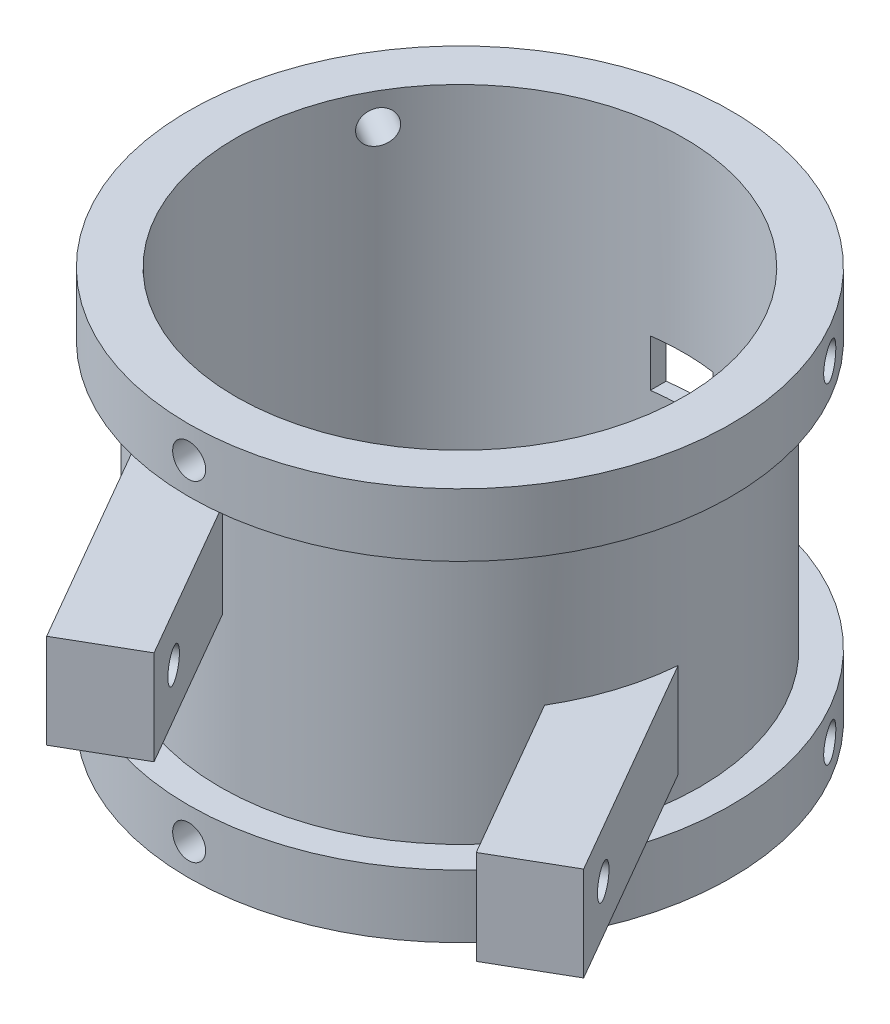
SolidWorks part; units mm, degrees
note: The reader was unsure of these and kept them because the rebuilt part matched: shared geometry of "Sketch2<3>", "Sketch2<4>", "Sketch2<5>".
ref_plane "Płaszczyzna przednia" through (0, 0, 0) normal (0, 0, 1) x (1, 0, 0)
ref_plane "Płaszczyzna górna" through (0, 0, 0) normal (0, 1, 0) x (1, 0, 0)
ref_plane "Płaszczyzna prawa" through (0, 0, 0) normal (1, 0, 0) x (0, 0, -1)
sketch "Sketch2" plane through (0, 0, 0) normal (0, 1, 0) x (1, 0, 0)
  line L0 (-9.6536, -4.1301) -> (-25.3067, -13.1675)
  line L1 (-1.25, 10.4253) -> (1.25, 10.4253)
  line L2 (-1.25, 10.4253) -> (-1.25, 28.5)
  line L3 (-1.25, 28.5) -> (1.25, 28.5)
  line L4 (1.25, 10.4253) -> (1.25, 28.5)
  line L5 (-8.4036, -6.2952) -> (-24.0567, -15.3325)
  line L6 (-8.4036, -6.2952) -> (-9.6536, -4.1301)
  line L7 (-24.0567, -15.3325) -> (-25.3067, -13.1675)
  line L8 (8.4036, -6.2952) -> (24.0567, -15.3325)
  line L9 (9.6536, -4.1301) -> (25.3067, -13.1675)
  line L10 (9.6536, -4.1301) -> (8.4036, -6.2952)
  line L11 (25.3067, -13.1675) -> (24.0567, -15.3325)
  circle A0 centre (0, 0) radius 5.25
  circle A1 centre (0, 0) radius 10.5
  circle A2 centre (0, 0) radius 28.5
  circle A3 centre (0, 0) radius 30.5
  circle A4 centre (0, 0) radius 34.5
  point P22 (0, 0)
  dimension "D1" = 10.5
  dimension "D2" = 21
  dimension "D3" = 57
  dimension "D5" = 2.5
  dimension "D4" = 2
  dimension "D7" = 4
  dimension "D6" = 3
extrude "Boss-Extrude1" add sketch "Sketch2" along normal blind 3 contours A1 A0 | L6 A1 | L1 A1 | L10 A1
hole_wizard "Ø3.0mm Dowel Hole1" positions "Sketch3" profile "Sketch4" hole size "Ø3.0" standard "ANSI Metric" end condition through all
sketch "Sketch3" plane through (0, 3, 0) normal (0, 1, 0) x (1, 0, 0)
  point P0 (0, 8)
  dimension "D1" = 8
sketch "Sketch4" plane through (0, 3, -8) normal (1, 0, 0) x (0, 0, 1)
  line L0 (0, 0) -> (0, 3)
  line L1 (0, 3) -> (1.5, 3)
  line L2 (1.5, 3) -> (1.5, 0)
  line L5 (1.5, 0) -> (0, 0)
  line L11 (0, -6.35) -> (0, 107.95) construction
  dimension "Thru Hole Dia." = 3
  dimension "Thru Hole Depth" = 3
pattern_circular "CirPattern1" count 4 over 360 about axis through (0, 0, 0) along (0, 1, 0) of "Ø3.0mm Dowel Hole1"
extrude "Boss-Extrude2" add sketch "Sketch2<3>" along normal blind 50 contours A3 | A2
sketch "Sketch2<3>" plane through (0, 0, 0) normal (0, 1, 0) x (1, 0, 0) same geometry as "Sketch2"
extrude "Boss-Extrude3" add sketch "Sketch2<4>" along normal blind 20 contours L8 A2 L9 A1 | L0 A2 L5 A1 | L4 L3 L2 L1
sketch "Sketch2<4>" plane through (0, 0, 0) normal (0, 1, 0) x (1, 0, 0) same geometry as "Sketch2"
chamfer "Chamfer1" distance 11 angle 57.8 3 edges at (-9.0933, 20, 5.25) (9.0933, 20, 5.25) (0, 20, -10.4253)
extrude "Boss-Extrude4" add sketch "Sketch2<5>" along normal blind 8 contours A4 | A3
sketch "Sketch2<5>" plane through (0, 0, 0) normal (0, 1, 0) x (1, 0, 0) same geometry as "Sketch2"
ref_plane "Plane1" through (0, 0, -30.5) normal (0, 0, -1) x (0, -1, 0)
sketch "Sketch5" plane through (0, 0, -30.5) normal (0, 0, -1) x (0, -1, 0)
  line L1 (-26.3456, -4) -> (-20.3456, -4)
  line L2 (-26.3456, -4) -> (-26.3456, 4)
  line L3 (-26.3456, 4) -> (-20.3456, 4)
  line L4 (-20.3456, -4) -> (-20.3456, 4)
  line L7 (0, 0) -> (-62.2372, 0) construction
  dimension "D1" = 6
  dimension "D2" = 8
extrude "Cut-Extrude1" cut sketch "Sketch5" against normal up to next
ref_plane "Plane2" through (0, 0, 34.5) normal (0, 0, 1) x (1, 0, 0)
sketch "Sketch6" plane through (0, 0, 34.5) normal (0, 0, 1) x (1, 0, 0)
  line L0 (0, 0) -> (0, 8) construction
  line L1 (34.5, 8) -> (-34.5, 8) construction
  circle A0 centre (0, 4) radius 2.1
  dimension "D1" = 4.2
extrude "Cut-Extrude2" cut sketch "Sketch6" against normal blind 10 contours A0
pattern_circular "CirPattern2" count 3 over 360 about axis through (0, 50, 0) along (0, 1, 0) of "Cut-Extrude2"
ref_plane "Plane3" through (0, 25, 0) normal (0, 1, 0) x (1, 0, 0)
mirror "Mirror4" about plane through (0, 25, 0) normal (0, 1, 0) of "CirPattern2", "Boss-Extrude4", "Cut-Extrude2"
ref_plane "Plane4" through (15.25, 0, 26.4138) normal (0.5, 0, 0.866) x (0.866, 0, -0.5)
sketch "Sketch7" plane through (15.25, 0, 26.4138) normal (0.5, 0, 0.866) x (0.866, 0, -0.5)
  line L0 (0, 0) -> (0, 60.7368) construction
  line L1 (-25, 39.1476) -> (-15, 39.1476)
  line L2 (-25, 39.1476) -> (-25, 27.1476)
  line L3 (-25, 27.1476) -> (-15, 27.1476)
  line L4 (-15, 39.1476) -> (-15, 27.1476)
  line L5 (15, 22.6526) -> (25, 22.6526)
  line L6 (15, 22.6526) -> (15, 10.6526)
  line L7 (15, 10.6526) -> (25, 10.6526)
  line L8 (25, 22.6526) -> (25, 10.6526)
  dimension "D1" = 10
  dimension "D2" = 12
  dimension "D3" = 15
extrude "Boss-Extrude5" add sketch "Sketch7" against normal up to surface and the other way offset from surface (19.8 mm away) 0.2 up to face at (0, 42, 30.5)
sketch "Sketch8" plane through (-21.6506, 0, 12.5) normal (-0.866, 0, 0.5) x (0.5, 0, 0.866)
  line L0 (50.3, 22.6526) -> (50.3, 10.6526) construction
  line L1 (43.5, 10.6526) -> (43.5, 22.6526) construction
  line L2 (26.5565, 10.6526) -> (50.3, 10.6526) construction
  line L3 (26.5565, 22.6526) -> (50.3, 22.6526) construction
  line L4 (43.5, 27.1476) -> (43.5, 39.1476) construction
  line L5 (17.4714, 27.1476) -> (50.3, 27.1476) construction
  line L6 (17.4714, 39.1476) -> (50.3, 39.1476) construction
  circle A0 centre (43.5, 16.6526) radius 2
  circle A1 centre (43.5, 33.1476) radius 2
  point P18 (0, 0)
  point P19 (43.5, 33.1476)
  point P20 (0, 0)
  point P21 (43.5, 16.6526)
  dimension "D1" = 4
  dimension "D2" = 6.8
extrude "Cut-Extrude3" cut sketch "Sketch8" against normal up to next
